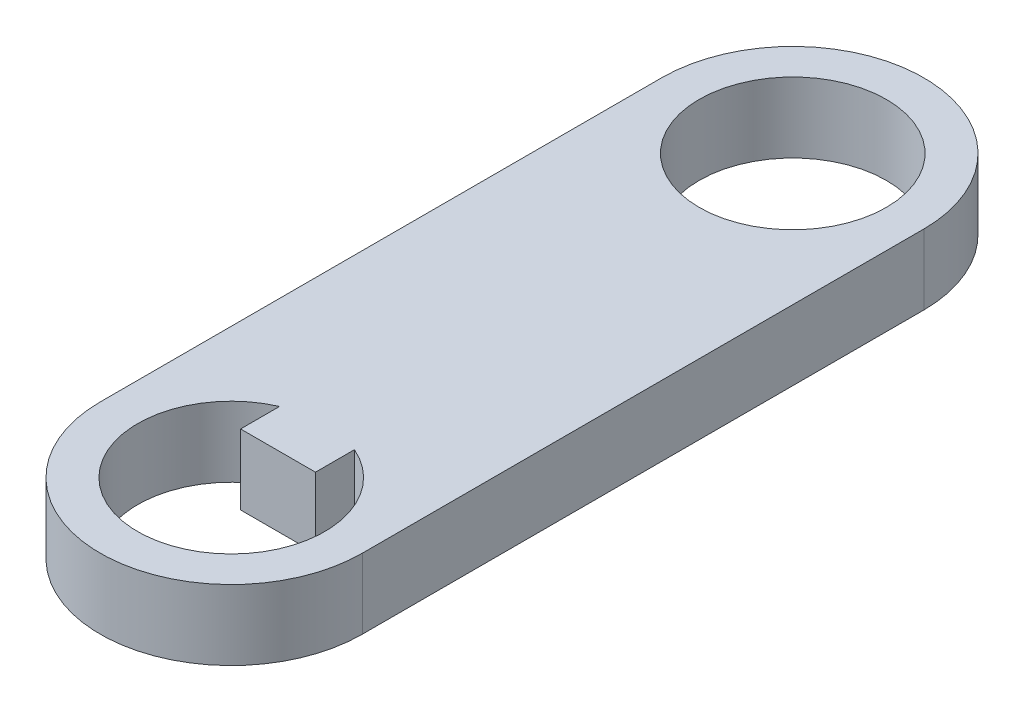
SolidWorks part; units mm, degrees
ref_plane "Front Plane" through (0, 0, 0) normal (0, 0, 1) x (1, 0, 0)
ref_plane "Top Plane" through (0, 0, 0) normal (0, 1, 0) x (1, 0, 0)
ref_plane "Right Plane" through (0, 0, 0) normal (1, 0, 0) x (0, 0, -1)
sketch "Sketch1" plane through (0, 0, 0) normal (0, 1, 0) x (1, 0, 0)
  line L0 (0, 60) -> (0, 0) construction
  line L1 (14, 60) -> (14, 0)
  line L2 (-14, 60) -> (-14, 0)
  line L4 (4, 5) -> (-4, 5)
  line L5 (4, 5) -> (4, 15)
  line L6 (4, 15) -> (-4, 15)
  line L7 (-4, 5) -> (-4, 15)
  line L8 (4, 5) -> (-4, 15) construction
  line L9 (4, 15) -> (-4, 5) construction
  arc A0 (14, 60) -> (-14, 60) centre (0, 60) ccw
  arc A1 (-14, 0) -> (14, 0) centre (0, 0) ccw
  circle A2 centre (0, 0) radius 10
  circle A3 centre (0, 60) radius 10
  point P2 (0, 30)
  point P9 (0, 10)
  dimension "D1" = 20
  dimension "D2" = 20
  dimension "D4" = 14
  dimension "D3" = 60
  dimension "D5" = 8
  dimension "D6" = 10
extrude "Boss-Extrude1" add sketch "Sketch1" along normal blind 7.5 contours L2 A1 L1 A0 A3 A2 L7 L6 L5 | L5 L4 L7 L6 region at (0, 0, -30.458)
equation "\"shaftDiam\" = 20mm"
equation "\"keyW\" = 8mm"
equation "\"keyL\" = 10mm"
equation "\"clearance\" = 1mm"
equation "\"handleShaftLen\" = 60mm"
equation "\"D1@Sketch1\"=\"shaftDiam\""
equation "\"D2@Sketch1\"=\"shaftDiam\""
equation "\"D3@Sketch1\"=\"handleShaftLen\""
equation "\"D4@Sketch1\"=\"shaftDiam\"*.7"
equation "\"D5@Sketch1\"=\"keyW\""
equation "\"D6@Sketch1\"=\"keyL\""
equation "\"D1@Boss-Extrude1\"=\"handleShaftLen\"/8"
